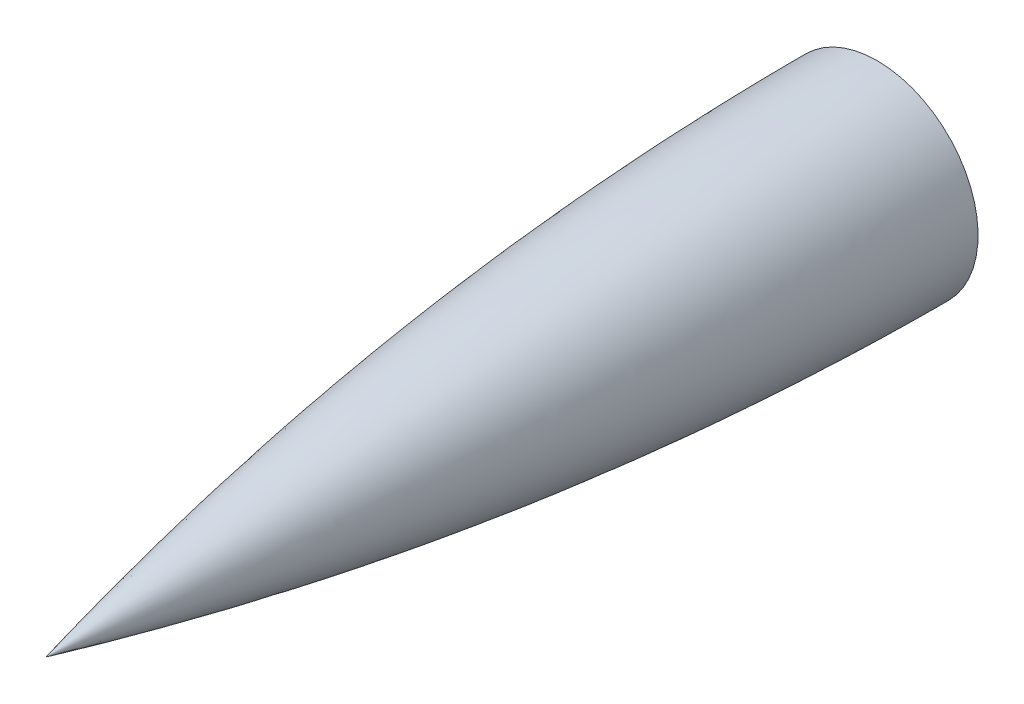
SolidWorks part; units mm, degrees
ref_plane "Front Plane" through (0, 0, 0) normal (0, 0, 1) x (1, 0, 0)
ref_plane "Top Plane" through (0, 0, 0) normal (0, 1, 0) x (1, 0, 0)
ref_plane "Right Plane" through (0, 0, 0) normal (1, 0, 0) x (0, 0, -1)
sketch "Sketch1" plane through (0, 0, 0) normal (1, 0, 0) x (0, 0, -1)
  line L0 (0, 50.8) -> (0, 0)
  line L1 (0, 0) -> (-419.1, 0)
  spline S0 degree 2 poles (-460.1592, -10.4413) (-209.1246, 56.3777) (41.91, 50.292) knots 0 0 0 1 1 1 construction
  spline S1 degree 2 poles (-419.1, 0) (-209.55, 50.8) (0, 50.8) knots 0.08178 0.08178 0.08178 0.916525 0.916525 0.916525
  dimension "D1" = 50.8
revolve "Revolve1" add sketch "Sketch1" angle 360 about L1
equation "\"Kprime\"= 1"
equation "\"R\"= 2'radius of the base"
equation "\"L\"= 16.5'overall length"
